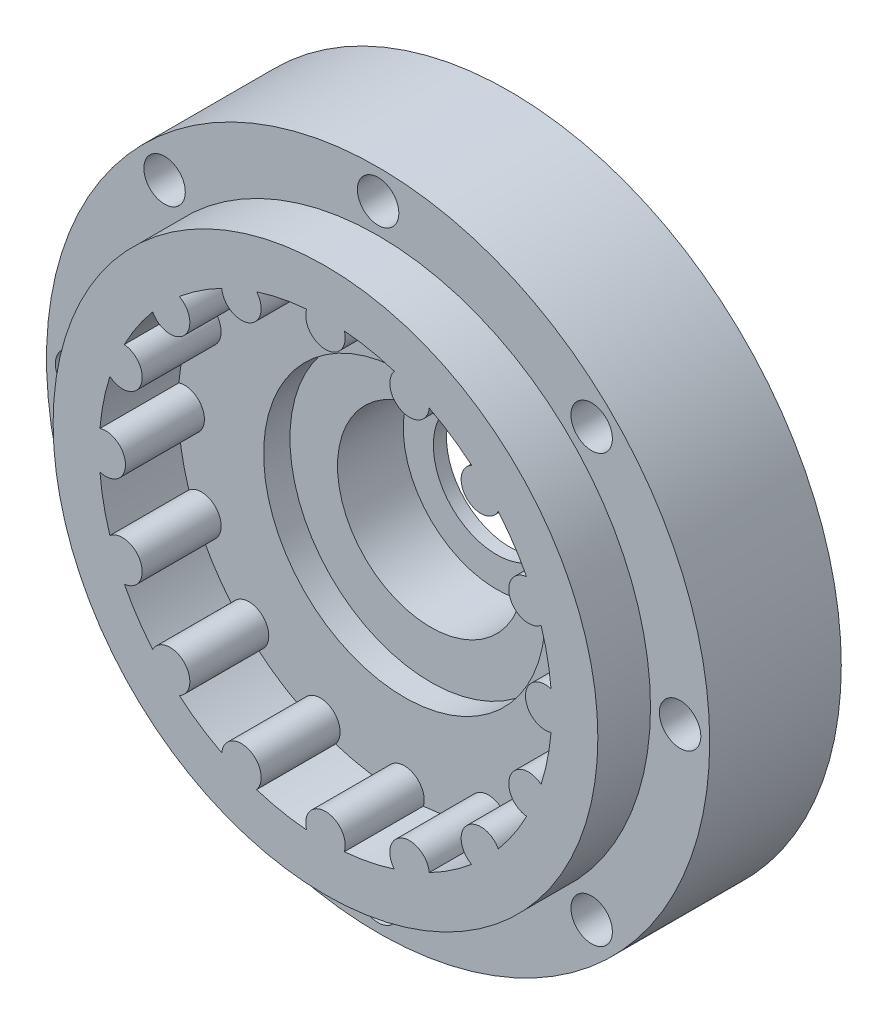
SolidWorks part; units mm, degrees
material "ABS"
ref_plane "Front Plane" through (0, 0, 0) normal (0, 0, 1) x (1, 0, 0)
ref_plane "Top Plane" through (0, 0, 0) normal (0, 1, 0) x (1, 0, 0)
ref_plane "Right Plane" through (0, 0, 0) normal (1, 0, 0) x (0, 0, -1)
sketch "Sketch1" plane through (0, 0, 0) normal (0, 0, 1) x (1, 0, 0)
  circle A0 centre (0, 0) radius 32.004
  dimension "D1" = 64.008
extrude "Boss-Extrude1" add sketch "Sketch1" along normal blind 12.7
sketch "Sketch2" plane through (0, 0, 12.7) normal (0, 0, 1) x (1, 0, 0)
  circle A0 centre (0, 0) radius 26.289
  circle A1 centre (0, 0) radius 32.004
  circle A2 centre (0, 0) radius 32.004
  dimension "D1" = 0
  dimension "D2" = 5.715
extrude "Cut-Extrude1" cut sketch "Sketch2" against normal blind 2.54 flip side to cut
sketch "Sketch3" plane through (0, 0, 10.16) normal (0, 0, 1) x (1, 0, 0)
  line L0 (0, 0) -> (0, 21.209) construction
  circle A1 centre (0, 21.209) radius 1.905
  circle A3 centre (0, 0) radius 21.209 construction
  circle A13 centre (8.1163, 19.5946) radius 1.905
  circle A14 centre (14.997, 14.997) radius 1.905
  circle A15 centre (19.5946, 8.1163) radius 1.905
  circle A16 centre (21.209, 0) radius 1.905
  circle A17 centre (19.5946, -8.1163) radius 1.905
  circle A18 centre (14.997, -14.997) radius 1.905
  circle A19 centre (8.1163, -19.5946) radius 1.905
  circle A20 centre (0, -21.209) radius 1.905
  circle A21 centre (-8.1163, -19.5946) radius 1.905
  circle A22 centre (-14.997, -14.997) radius 1.905
  circle A23 centre (-19.5946, -8.1163) radius 1.905
  circle A24 centre (-21.209, 0) radius 1.905
  circle A25 centre (-19.5946, 8.1163) radius 1.905
  circle A26 centre (-14.997, 14.997) radius 1.905
  circle A27 centre (-8.1163, 19.5946) radius 1.905
  dimension "D2" = 3.81
  dimension "D3" = 16
  dimension "D1" = 42.418
  dimension "D4" = 21.209
sketch "Sketch4" plane through (0, 0, 10.16) normal (0, 0, 1) x (1, 0, 0)
  circle A39 centre (0, 0) radius 27.559 construction
  circle A40 centre (0, 0) radius 13.589
  circle A41 centre (0, 0) radius 26.289 construction
  dimension "D2" = 55.118
  dimension "D1" = 13.97
extrude "Cut-Extrude3" cut sketch "Sketch4" against normal blind 2.54 contours A40 region at (0, 0, 10.16)
sketch "Sketch5" plane through (0, 0, 7.62) normal (0, 0, 1) x (1, 0, 0)
  circle A0 centre (0, 0) radius 9
  circle A1 centre (0, 0) radius 6.1
  dimension "D1" = 18
  dimension "D2" = 12.2
extrude "Cut-Extrude4" cut sketch "Sketch5" against normal through all contours A1 region at (0, 0, 7.62)
sketch "Sketch6" plane through (0, 0, 12.7) normal (0, 0, 1) x (1, 0, 0)
  line L0 (0, 0) -> (0, 32.004) construction
  line L1 (0, 0) -> (22.6302, 22.6302) construction
  line L2 (0, 0) -> (32.004, 0) construction
  line L3 (0, 0) -> (22.6302, -22.6302) construction
  line L4 (0, 0) -> (0, -32.004) construction
  line L5 (0, 0) -> (-22.6302, -22.6302) construction
  line L6 (0, 0) -> (-32.004, 0) construction
  line L7 (0, 0) -> (-22.6302, 22.6302) construction
  line L8 (0, 0) -> (0, 29.1465) construction
  circle A0 centre (0, 0) radius 32.004 construction
  circle A1 centre (0, 29.1465) radius 2
  circle A2 centre (20.6097, 20.6097) radius 2
  circle A3 centre (29.1465, 0) radius 2
  circle A4 centre (20.6097, -20.6097) radius 2
  circle A5 centre (0, -29.1465) radius 2
  circle A6 centre (-20.6097, -20.6097) radius 2
  circle A7 centre (-29.1465, 0) radius 2
  circle A8 centre (-20.6097, 20.6097) radius 2
  point P6 (0, 29.1465)
  point P16 (20.6097, 20.6097)
  point P18 (29.1465, 0)
  point P20 (20.6097, -20.6097)
  point P22 (0, -29.1465)
  point P24 (-20.6097, -20.6097)
  point P26 (-29.1465, 0)
  point P28 (-20.6097, 20.6097)
  point P52 (0, 0)
  point P53 (0, 0)
  point P54 (20.6097, 20.6097)
  dimension "D3" = 4
  dimension "D1" = 29.1465
  dimension "D2" = 8
  dimension "D4" = 8
extrude "Cut-Extrude5" cut sketch "Sketch5<3>" against normal blind 6.35
sketch "Sketch5<3>" plane through (0, 0, 7.62) normal (0, 0, 1) x (1, 0, 0) same geometry as "Sketch5"
sketch "Sketch8" plane through (0, 0, 10.16) normal (0, 0, 1) x (1, 0, 0)
  circle A0 centre (0, 0) radius 21.844
  circle A1 centre (0, 0) radius 26.289
  circle A5 centre (0, 0) radius 26.289
  dimension "D1" = 0
extrude "Boss-Extrude2" add sketch "Sketch8" along normal blind 7.62
extrude "Boss-Extrude3" add sketch "Sketch3" along normal blind 7.62
extrude "Cut-Extrude6" cut sketch "Sketch6" against normal through all
